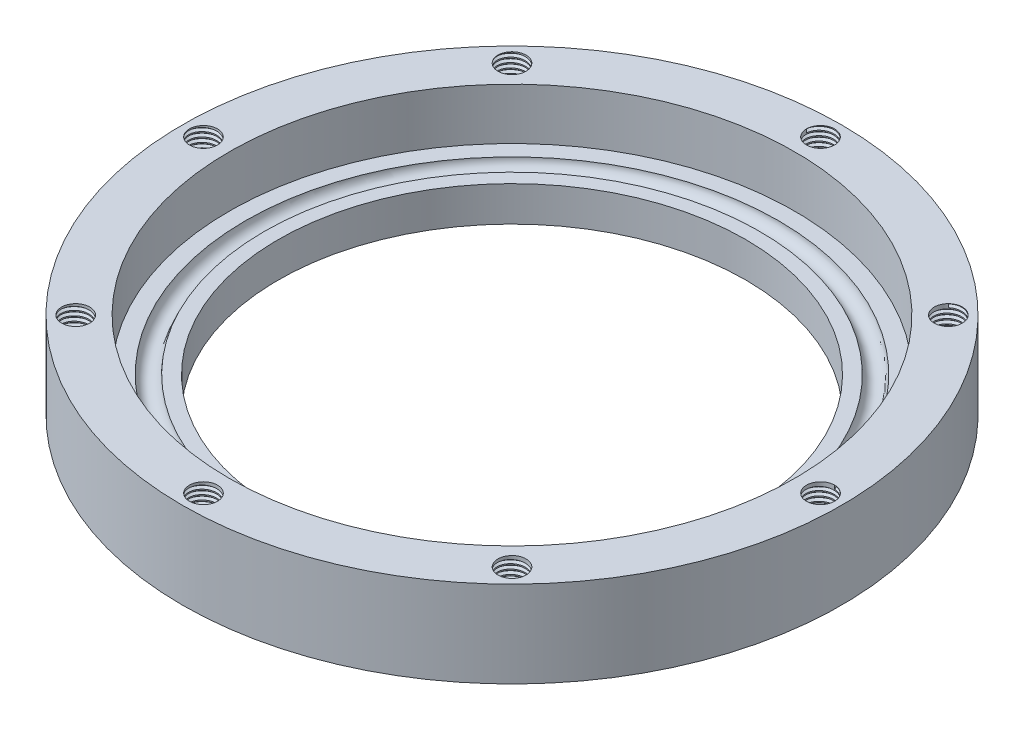
SolidWorks part; units mm, degrees
ref_plane "Front Plane" through (0, 0, 0) normal (0, 0, 1) x (1, 0, 0)
ref_plane "Top Plane" through (0, 0, 0) normal (0, 1, 0) x (1, 0, 0)
ref_plane "Right Plane" through (0, 0, 0) normal (1, 0, 0) x (0, 0, -1)
sketch "Sketch2" plane through (0, 0, 0) normal (0, 1, 0) x (1, 0, 0)
  circle A0 centre (0, 0) radius 60.5
  circle A1 centre (0, 0) radius 70.5
  dimension "D1" = 121
  dimension "D2" = 10
extrude "Boss-Extrude3" add sketch "Sketch2" along normal blind 11 contours A1 A0
sketch "Sketch3" plane through (0, 0, 0) normal (0, -1, 0) x (1, 0, 0)
  circle A0 centre (0, 0) radius 70.5
  circle A1 centre (0, 0) radius 50
  dimension "D1" = 100
extrude "Boss-Extrude4" add sketch "Sketch3" along normal blind 7.5
sketch "Sketch4" plane through (0, 11, 0) normal (0, 1, 0) x (1, 0, 0)
  line L0 (0, 66) -> (0, 0) construction
  line L1 (0, 0) -> (46.669, 46.669) construction
  circle A0 centre (0, 66) radius 3
  circle A1 centre (46.669, 46.669) radius 3
  circle A2 centre (66, 0) radius 3
  circle A3 centre (46.669, -46.669) radius 3
  circle A4 centre (0, -66) radius 3
  circle A5 centre (-46.669, -46.669) radius 3
  circle A6 centre (-66, 0) radius 3
  circle A7 centre (-46.669, 46.669) radius 3
  point P0 (0, 66)
  point P6 (46.669, 46.669)
  point P8 (66, 0)
  point P10 (46.669, -46.669)
  point P12 (0, -66)
  point P14 (-46.669, -46.669)
  point P20 (0, 0)
  dimension "D1" = 6
  dimension "D2" = 66
  dimension "D4" = 45
  dimension "D3" = 8
extrude "Cut-Extrude1" cut sketch "Sketch4" against normal blind 5
thread "Thread1" pitch 1 start angle 0, offset 0, length 5, pitch 1, diameter 6
ref_plane "Plane1" through (-3, 11, -66) normal (0, 0, 1) x (-1, 0, 0)
sketch "Thread Profile1" plane through (-3, 11, -66) normal (0, 0, 1) x (-1, 0, 0)
  line L0 (0, 0) -> (0, 1) construction
  line L1 (0, 0) -> (0.5413, 0.3125)
  line L2 (0.5413, 0.3125) -> (0.5413, 0.4375)
  line L3 (0.5413, 0.4375) -> (0, 0.75)
  line L4 (0.5413, 0.375) -> (0, 0.375) construction
  line L11 (0, 0) -> (0, 0.75)
  point P2 (0, 0)
  dimension "Pitch" = 1
  dimension "Profile_Angle" = 60
  dimension "Profile_Land" = 0.125
  dimension "Profile_Height" = 0.5413
pattern_circular "CirPattern1" count 8 over 360 of "Thread1"
sketch "Sketch5" plane through (0, 0, 0) normal (0, 0, 1) x (1, 0, 0)
  line L0 (-55, -7.5) -> (-55, 0) construction
  line L2 (-55, 0) -> (0, 0)
  circle A0 centre (-55, 0) radius 2
  dimension "D2" = 4
  dimension "D1" = 7.5
  dimension "D3" = 55
sketch "Sketch6" plane through (0, 0, 0) normal (0, 1, 0) x (1, 0, 0)
  circle A0 centre (0, 0) radius 55
  dimension "D1" = 110
sweep "Cut-Sweep1" cut profiles "Sketch5" path "Sketch6"
